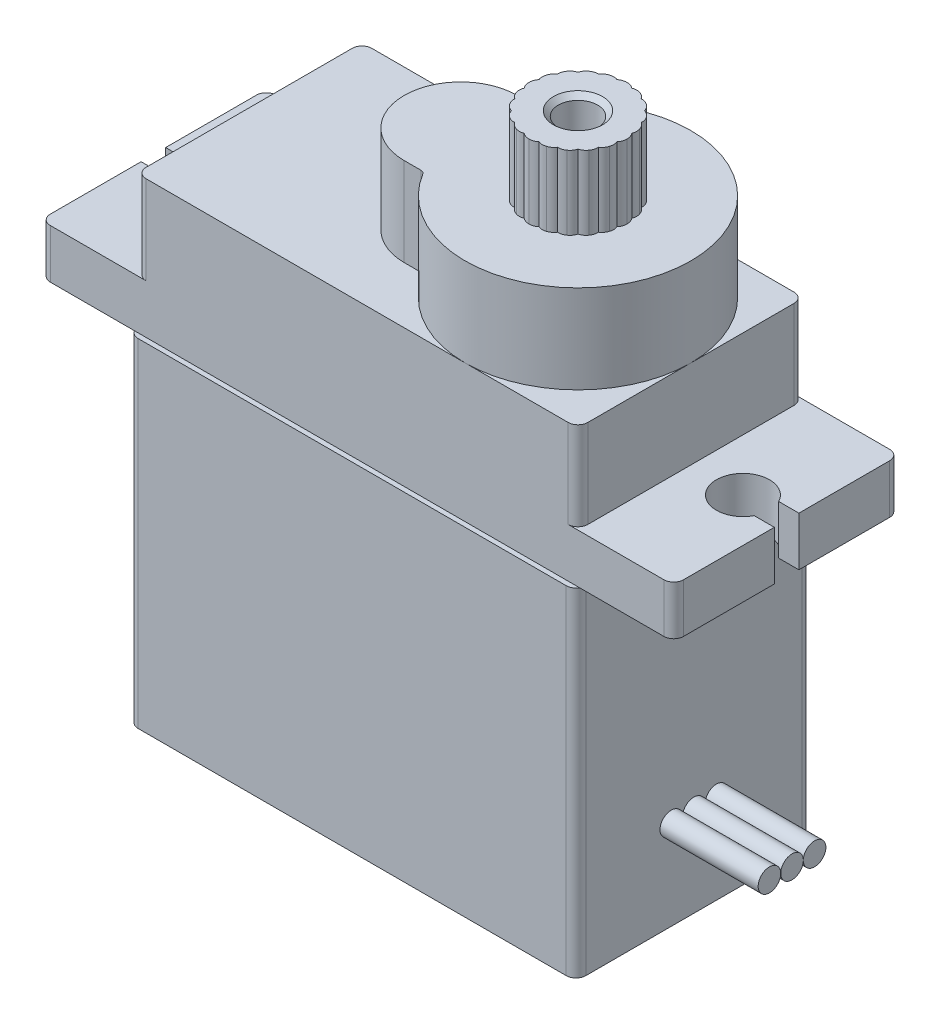
SolidWorks part; units mm, degrees
ref_plane "Ön Düzlem" through (0, 0, 0) normal (0, 0, 1) x (1, 0, 0)
ref_plane "Üst Düzlem" through (0, 0, 0) normal (0, 1, 0) x (1, 0, 0)
ref_plane "Sağ Düzlem" through (0, 0, 0) normal (1, 0, 0) x (0, 0, -1)
sketch "Sketch1" plane through (0, 0, 0) normal (0, 1, 0) x (1, 0, 0)
  line L1 (-11.4, -6) -> (11.4, -6)
  line L2 (-11.4, -6) -> (-11.4, 6)
  line L3 (-11.4, 6) -> (11.4, 6)
  line L4 (11.4, -6) -> (11.4, 6)
  line L5 (-11.4, -6) -> (11.4, 6) construction
  line L6 (-11.4, 6) -> (11.4, -6) construction
  point P0 (0, 0)
  dimension "D1" = 22.8
  dimension "D2" = 12
extrude "Boss-Extrude1" add sketch "Sketch1" along normal blind 17.2
sketch "Sketch2" plane through (0, 17.2, 0) normal (0, 1, 0) x (1, 0, 0)
  line L0 (-11.4, 6) -> (-11.4, -6) construction
  line L1 (-16.125, -5.75) -> (16.125, -5.75)
  line L2 (-16.125, -5.75) -> (-16.125, -0.625)
  line L3 (-16.125, 5.75) -> (16.125, 5.75)
  line L4 (16.125, -5.75) -> (16.125, -0.625)
  line L5 (-16.125, -5.75) -> (16.125, 5.75) construction
  line L6 (-16.125, 5.75) -> (16.125, -5.75) construction
  line L7 (0, -5.75) -> (0, 5.75) construction
  line L8 (-16.125, 0.625) -> (-16.125, 5.75)
  line L9 (-15.0966, 0.625) -> (-16.125, 0.625)
  line L10 (-15.0966, -0.625) -> (-16.125, -0.625)
  line L11 (-15.6108, 0.625) -> (-15.6108, -0.625) construction
  line L12 (15.0966, 0.625) -> (16.125, 0.625)
  line L13 (15.0966, -0.625) -> (16.125, -0.625)
  line L14 (16.125, 0.625) -> (16.125, 5.75)
  arc A0 (-15.0966, -0.625) -> (-15.0966, 0.625) centre (-13.9, 0) ccw
  arc A1 (15.0966, -0.625) -> (15.0966, 0.625) centre (13.9, 0) cw
  point P0 (0, 0)
  point P10 (-15.6108, 0)
  point P14 (0, 0)
  dimension "D5" = 2.7
  dimension "D1" = 11.5
  dimension "D2" = 32.25
  dimension "D3" = 4.725
  dimension "D4" = 2.5
  dimension "D6" = 1.25
extrude "Boss-Extrude2" add sketch "Sketch2" along normal blind 2.5
sketch "Sketch3" plane through (0, 19.7, 0) normal (0, 1, 0) x (1, 0, 0)
  line L0 (11.4, 5.75) -> (-11.4, 5.75) construction
  line L1 (-11.25, -5.75) -> (11.25, -5.75)
  line L2 (-11.25, -5.75) -> (-11.25, 5.75)
  line L3 (-11.25, 5.75) -> (11.25, 5.75)
  line L4 (11.25, -5.75) -> (11.25, 5.75)
  line L5 (-11.25, -5.75) -> (11.25, 5.75) construction
  line L6 (-11.25, 5.75) -> (11.25, -5.75) construction
  line L7 (-16.125, 5.75) -> (-16.125, 0.625) construction
  point P0 (0, 0)
  dimension "D1" = 22.5
  dimension "D2" = 4.875
extrude "Boss-Extrude3" add sketch "Sketch3" along normal blind 4.5
sketch "Sketch4" plane through (0, 24.2, 0) normal (0, 1, 0) x (1, 0, 0)
  line L0 (11.25, 5.75) -> (-11.25, 5.75) construction
  line L2 (-11.4, -5.75) -> (11.4, -5.75) construction
  line L4 (11.25, -5.75) -> (11.25, 5.75) construction
  line L5 (-0.475, 2.875) -> (0.378, 2.875)
  line L6 (-0.475, -2.875) -> (0.378, -2.875)
  arc A0 (0.5915, -2.9948) -> (0.5915, 2.9948) centre (5.5, 0) ccw
  arc A1 (-0.475, 2.875) -> (-0.475, -2.875) centre (-0.475, 0) ccw
  arc A2 (0.5915, -2.9948) -> (0.378, -2.875) centre (0.378, -3.125) ccw
  arc A3 (0.5915, 2.9948) -> (0.378, 2.875) centre (0.378, 3.125) cw
  dimension "D1" = 5.975
  dimension "D2" = 5.75
  dimension "D3" = 0.25
extrude "Boss-Extrude4" add sketch "Sketch4" along normal blind 4.5
sketch "Sketch5" plane through (0, 28.7, 0) normal (0, 1, 0) x (1, 0, 0)
  arc A1 (3.1357, 0.3745) -> (3.0053, 0) centre (3.5651, 0.015) ccw
  arc A2 (3.1357, -0.3745) -> (3.0053, 0) centre (3.5651, -0.015) cw
  circle A3 centre (5.5, 0) radius 2.375 construction
  arc A4 (3.3671, 1.0868) -> (3.1274, 0.7709) centre (3.6644, 0.6122) ccw
  arc A5 (3.1357, 0.3745) -> (3.1274, 0.7709) centre (3.6551, 0.5837) cw
  arc A6 (3.8073, 1.6927) -> (3.4817, 1.4664) centre (3.9434, 1.1495) ccw
  arc A7 (3.3671, 1.0868) -> (3.4817, 1.4664) centre (3.9258, 1.1252) cw
  arc A8 (4.4132, 2.1329) -> (4.0336, 2.0183) centre (4.3748, 1.5742) ccw
  arc A9 (3.8073, 1.6927) -> (4.0336, 2.0183) centre (4.3505, 1.5566) cw
  arc A10 (5.1255, 2.3643) -> (4.7291, 2.3726) centre (4.9163, 1.8449) ccw
  arc A11 (4.4132, 2.1329) -> (4.7291, 2.3726) centre (4.8878, 1.8356) cw
  arc A12 (5.8745, 2.3643) -> (5.5, 2.4947) centre (5.515, 1.9349) ccw
  arc A13 (5.1255, 2.3643) -> (5.5, 2.4947) centre (5.485, 1.9349) cw
  arc A14 (6.5868, 2.1329) -> (6.2709, 2.3726) centre (6.1122, 1.8356) ccw
  arc A15 (5.8745, 2.3643) -> (6.2709, 2.3726) centre (6.0837, 1.8449) cw
  arc A16 (7.1927, 1.6927) -> (6.9664, 2.0183) centre (6.6495, 1.5566) ccw
  arc A17 (6.5868, 2.1329) -> (6.9664, 2.0183) centre (6.6252, 1.5742) cw
  arc A18 (7.6329, 1.0868) -> (7.5183, 1.4664) centre (7.0742, 1.1252) ccw
  arc A19 (7.1927, 1.6927) -> (7.5183, 1.4664) centre (7.0566, 1.1495) cw
  arc A20 (7.8643, 0.3745) -> (7.8726, 0.7709) centre (7.3449, 0.5837) ccw
  arc A21 (7.6329, 1.0868) -> (7.8726, 0.7709) centre (7.3356, 0.6122) cw
  arc A22 (7.8643, -0.3745) -> (7.9947, 0) centre (7.4349, -0.015) ccw
  arc A23 (7.8643, 0.3745) -> (7.9947, 0) centre (7.4349, 0.015) cw
  arc A24 (7.6329, -1.0868) -> (7.8726, -0.7709) centre (7.3356, -0.6122) ccw
  arc A25 (7.8643, -0.3745) -> (7.8726, -0.7709) centre (7.3449, -0.5837) cw
  arc A26 (7.1927, -1.6927) -> (7.5183, -1.4664) centre (7.0566, -1.1495) ccw
  arc A27 (7.6329, -1.0868) -> (7.5183, -1.4664) centre (7.0742, -1.1252) cw
  arc A28 (6.5868, -2.1329) -> (6.9664, -2.0183) centre (6.6252, -1.5742) ccw
  arc A29 (7.1927, -1.6927) -> (6.9664, -2.0183) centre (6.6495, -1.5566) cw
  arc A30 (5.8745, -2.3643) -> (6.2709, -2.3726) centre (6.0837, -1.8449) ccw
  arc A31 (6.5868, -2.1329) -> (6.2709, -2.3726) centre (6.1122, -1.8356) cw
  arc A32 (5.1255, -2.3643) -> (5.5, -2.4947) centre (5.485, -1.9349) ccw
  arc A33 (5.8745, -2.3643) -> (5.5, -2.4947) centre (5.515, -1.9349) cw
  arc A34 (4.4132, -2.1329) -> (4.7291, -2.3726) centre (4.8878, -1.8356) ccw
  arc A35 (5.1255, -2.3643) -> (4.7291, -2.3726) centre (4.9163, -1.8449) cw
  arc A36 (3.8073, -1.6927) -> (4.0336, -2.0183) centre (4.3505, -1.5566) ccw
  arc A37 (4.4132, -2.1329) -> (4.0336, -2.0183) centre (4.3748, -1.5742) cw
  arc A38 (3.3671, -1.0868) -> (3.4817, -1.4664) centre (3.9258, -1.1252) ccw
  arc A39 (3.8073, -1.6927) -> (3.4817, -1.4664) centre (3.9434, -1.1495) cw
  arc A40 (3.1357, -0.3745) -> (3.1274, -0.7709) centre (3.6551, -0.5837) ccw
  arc A41 (3.3671, -1.0868) -> (3.1274, -0.7709) centre (3.6644, -0.6122) cw
  arc A82 (5.5, -5.75) -> (11.25, 0) centre (5.5, 0) ccw construction
  arc A83 (5.5, -5.75) -> (11.25, 0) centre (5.5, 0) ccw construction
  circle A84 centre (5.5, 0) radius 1
  point P106 (5.5, 0)
  dimension "D1" = 2
  dimension "D3" = 0.56
  dimension "D4" = 4.75
extrude "Boss-Extrude5" add sketch "Sketch5" along normal blind 3.75 separate body
chamfer "Chamfer1" distance 0.25 angle 45 1 edges at (5.5, 32.45, 1)
fillet "Fillet1" radius 0.5 12 edges at (-11.4, 8.6, -6) (-11.4, 8.6, 6) (11.4, 8.6, -6) (11.4, 8.6, 6) (11.25, 21.95, -5.75) (11.25, 21.95, 5.75) (-11.25, 21.95, 5.75) (-11.25, 21.95, -5.75) (-16.125, 18.45, -5.75) (-16.125, 18.45, 5.75) (16.125, 18.45, -5.75) (16.125, 18.45, 5.75)
sketch "Sketch7" plane through (11.4, 0, 0) normal (1, 0, 0) x (0, 0, -1)
  circle A0 centre (0, 4.55) radius 0.575
  circle A1 centre (1.15, 4.55) radius 0.575
  circle A2 centre (-1.15, 4.55) radius 0.575
  dimension "D2" = 1.15
  dimension "D1" = 4.55
extrude "Boss-Extrude6" add sketch "Sketch7" along normal blind 5 separate body contours A2 region at (11.4, 4.55, 1.15)
extrude "Boss-Extrude7" add sketch "Sketch7<3>" along normal blind 5 separate body contours A0 region at (11.4, 4.55, 0)
sketch "Sketch7<3>" plane through (11.4, 0, 0) normal (1, 0, 0) x (0, 0, -1) same geometry as "Sketch7"
extrude "Boss-Extrude8" add sketch "Sketch7<4>" along normal blind 5 separate body contours A1 region at (11.4, 4.55, -1.15)
sketch "Sketch7<4>" plane through (11.4, 0, 0) normal (1, 0, 0) x (0, 0, -1) same geometry as "Sketch7"
